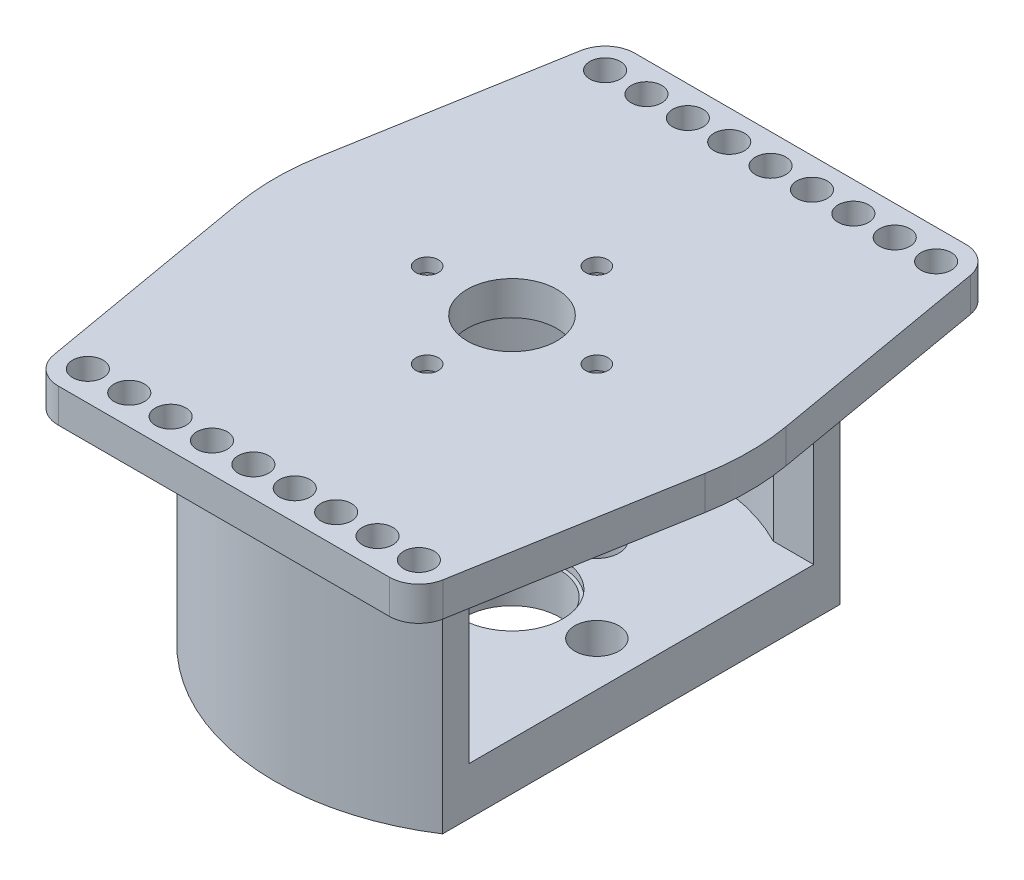
SolidWorks part; units mm, degrees
note: The reader was unsure of these and kept them because the rebuilt part matched: shared geometry of "Sketch3<3>".
ref_plane "Front Plane" through (0, 0, 0) normal (0, 0, 1) x (1, 0, 0)
ref_plane "Top Plane" through (0, 0, 0) normal (0, 1, 0) x (1, 0, 0)
ref_plane "Right Plane" through (0, 0, 0) normal (1, 0, 0) x (0, 0, -1)
sketch "Sketch1" plane through (0, 0, 0) normal (0, 1, 0) x (1, 0, 0)
  circle A0 centre (0, 0) radius 34.925
  circle A2 centre (0, 0) radius 7
  dimension "D1" = 14
  dimension "D2" = 69.85
extrude "Boss-Extrude1" add sketch "Sketch1" along normal blind 7.032
sketch "Sketch2" plane through (0, 7.032, 0) normal (0, 1, 0) x (1, 0, 0)
  circle A0 centre (0, 0) radius 7.5
  dimension "D1" = 15
extrude "Cut-Extrude1" cut sketch "Sketch2" against normal blind 1
sketch "Sketch3" plane through (0, 7.032, 0) normal (0, 1, 0) x (1, 0, 0)
  line L5 (19.05, 29.2721) -> (19.05, -29.2721)
  line L6 (13.0909, 25.4) -> (19.05, 25.4)
  line L7 (13.0909, -25.4) -> (19.05, -25.4)
  arc A0 (19.05, 29.2721) -> (19.05, -29.2721) centre (0, 0) ccw
  circle A1 centre (0, 0) radius 34.925 construction
  arc A2 (13.0909, 25.4) -> (13.0909, -25.4) centre (0, 0) ccw
  dimension "D1" = 6.35
  dimension "D2" = 19.05
  dimension "D3" = 50.8
extrude "Boss-Extrude2" add sketch "Sketch3" along normal blind 30
extrude "Cut-Extrude2" cut sketch "Sketch3<3>" against normal through all
sketch "Sketch3<3>" plane through (0, 7.032, 0) normal (0, 1, 0) x (1, 0, 0) same geometry as "Sketch3"
sketch "Sketch6" plane through (0, 37.032, 0) normal (0, 1, 0) x (1, 0, 0)
  line L1 (0, 12.5) -> (-12.5, 0) construction
  line L2 (-12.5, 0) -> (0, -12.5) construction
  line L3 (0, -12.5) -> (12.5, 0) construction
  line L4 (12.5, 0) -> (0, 12.5) construction
  circle A0 centre (0, 0) radius 12.5 construction
  circle A1 centre (0, 0) radius 6.6
  circle A2 centre (0, 0) radius 34.925
  arc A3 (19.05, 29.2721) -> (19.05, -29.2721) centre (0, 0) ccw construction
  dimension "D1" = 13.2
  dimension "D2" = 25
extrude "Boss-Extrude6" add sketch "Sketch6" along normal blind 5
hole_wizard "CBORE for M3 SHCS1" positions "Sketch7" profile "Sketch8" counterbore size "M3" standard "ANSI Metric"
sketch "Sketch7" plane through (0, 37.032, 0) normal (0, -1, 0) x (-1, 0, 0)
  point P0 (-12.5, 0)
  point P3 (0, -12.5)
  point P6 (0, 12.5)
  point P9 (12.5, 0)
sketch "Sketch8" plane through (12.5, 37.032, 0) normal (1, 0, 0) x (0, 0, -1)
  line L0 (0, 0) -> (0, 5)
  line L1 (0, 5) -> (1.65, 5)
  line L3 (1.65, 5) -> (1.65, 3)
  line L4 (1.65, 3) -> (3.25, 3)
  line L5 (3.25, 3) -> (3.25, 0)
  line L7 (3.25, 0) -> (0, 0)
  line L11 (0, -6.35) -> (0, 107.95) construction
  dimension "Thru Hole Dia." = 3.3
  dimension "Thru Hole Depth" = 5
  dimension "C'Bore Dia." = 6.5
  dimension "C'Bore Depth" = 3
sketch "Sketch9" plane through (0, 37.032, 0) normal (0, -1, 0) x (1, 0, 0)
  circle A0 centre (0, 12.5) radius 3.25
  circle A1 centre (12.5, 0) radius 3.25
  circle A2 centre (0, -12.5) radius 3.25
  circle A3 centre (-12.5, 0) radius 3.25
  circle A4 centre (-12.5, 0) radius 3.25 construction
  circle A5 centre (0, 12.5) radius 3.25 construction
extrude "Cut-Extrude3" cut sketch "Sketch9" along normal through all
sketch "Sketch10" plane through (0, 42.032, 0) normal (0, 1, 0) x (1, 0, 0)
  line L0 (0, 38.1) -> (0, 0) construction
  line L1 (-24.384, 38.1) -> (-18.288, 38.1) construction
  line L2 (-28.6849, 38.849) -> (-34.4071, 5.9922)
  line L3 (-24.384, 42.4656) -> (24.384, 42.4656)
  line L4 (28.6849, 38.849) -> (34.4071, 5.9922)
  line L5 (-34.4071, 5.9922) -> (0, 34.925)
  line L6 (0, 34.925) -> (34.4071, 5.9922)
  circle A0 centre (-24.384, 38.1) radius 2.2479
  circle A1 centre (-18.288, 38.1) radius 2.2479
  circle A2 centre (-12.192, 38.1) radius 2.2479
  circle A3 centre (-6.096, 38.1) radius 2.2479
  circle A4 centre (0, 38.1) radius 2.2479
  circle A10 centre (-27.432, 45.72) radius 2.2479 construction
  circle A11 centre (-19.812, 45.72) radius 2.2479 construction
  circle A12 centre (-12.192, 45.72) radius 2.2479 construction
  circle A13 centre (-4.572, 45.72) radius 2.2479 construction
  circle A14 centre (3.048, 45.72) radius 2.2479 construction
  circle A15 centre (6.096, 38.1) radius 2.2479
  circle A16 centre (12.192, 38.1) radius 2.2479
  circle A17 centre (18.288, 38.1) radius 2.2479
  circle A35 centre (10.668, 45.72) radius 2.2479 construction
  circle A36 centre (18.288, 45.72) radius 2.2479 construction
  circle A37 centre (25.908, 45.72) radius 2.2479 construction
  circle A45 centre (24.384, 38.1) radius 2.2479
  arc A47 (-24.384, 42.4656) -> (-28.6849, 38.849) centre (-24.384, 38.1) ccw
  circle A48 centre (0, 0) radius 34.925 construction
  arc A49 (24.384, 42.4656) -> (28.6849, 38.849) centre (24.384, 38.1) cw
  circle A51 centre (-18.288, -38.1) radius 2.2479 [skipped]
  circle A52 centre (-12.192, -38.1) radius 2.2479 [skipped]
  circle A53 centre (-6.096, -38.1) radius 2.2479 [skipped]
  circle A54 centre (-24.384, -38.1) radius 2.2479 [skipped]
  circle A55 centre (6.096, -38.1) radius 2.2479 [skipped]
  circle A56 centre (12.192, -38.1) radius 2.2479 [skipped]
  circle A57 centre (18.288, -38.1) radius 2.2479 [skipped]
  circle A58 centre (24.384, -38.1) radius 2.2479 [skipped]
  circle A59 centre (0, -38.1) radius 2.2479 construction
  point P14 (0, 0)
  point P15 (0, 0)
  point P16 (0, 0)
  point P17 (0, 0)
  point P40 (0, 0)
  dimension "D1" = 4.4958
  dimension "D4" = 8
  dimension "D9" = 4.3656
  dimension "D5" = 7.62
  dimension "D6" = 6.096
  dimension "D7" = 38.1
  dimension "D8" = 7.62
  dimension "D2" = 9
  dimension "D3" = 2
extrude "Boss-Extrude7" add sketch "Sketch10" against normal up to surface (5 mm away) up to face at (12.5, 37.032, -3.25)
mirror "Mirror1" about plane through (0, 0, 0) normal (0, 0, 1) of "Boss-Extrude7"
